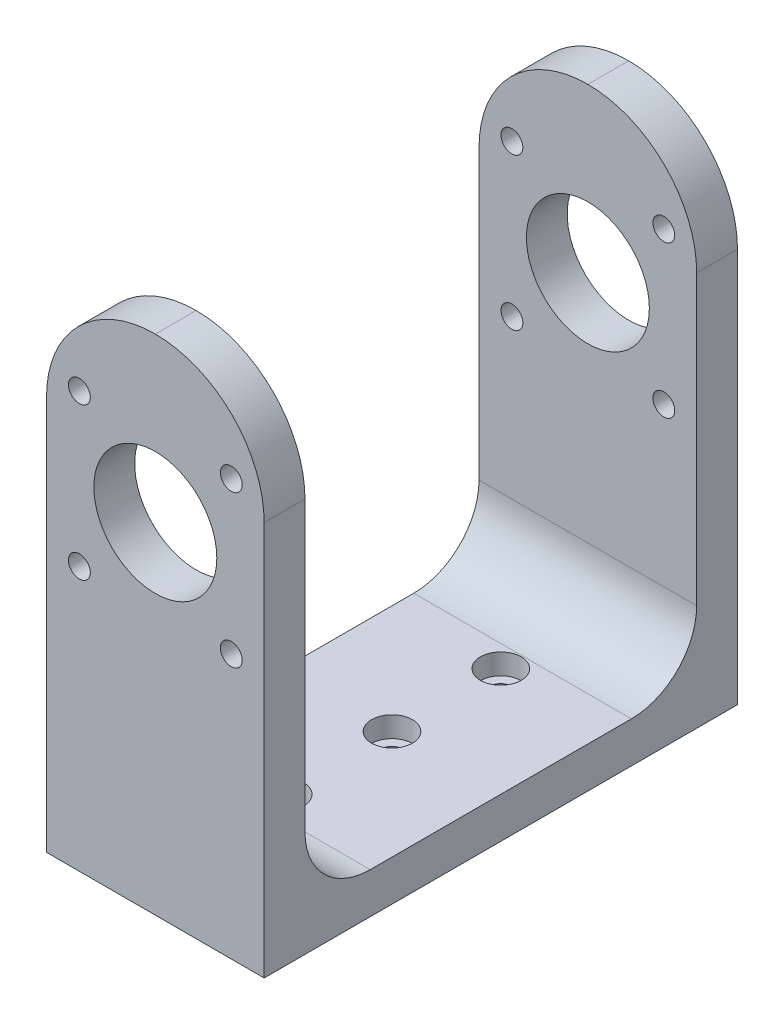
SolidWorks part; units mm, degrees
ref_plane "Front Plane" through (0, 0, 0) normal (0, 0, 1) x (1, 0, 0)
ref_plane "Top Plane" through (0, 0, 0) normal (0, 1, 0) x (1, 0, 0)
ref_plane "Right Plane" through (0, 0, 0) normal (1, 0, 0) x (0, 0, -1)
sketch "Sketch1" plane through (0, 0, 0) normal (0, 1, 0) x (1, 0, 0)
  line L1 (0, 0) -> (50.8, 0)
  line L2 (0, 0) -> (0, 110.49)
  line L3 (0, 110.49) -> (50.8, 110.49)
  line L4 (50.8, 0) -> (50.8, 110.49)
  dimension "D1" = 50.8
  dimension "D2" = 110.49
extrude "Boss-Extrude1" add sketch "Sketch1" along normal blind 9.525 contours L2 L1 L4 L3
sketch "Sketch2" plane through (0, 9.525, 0) normal (0, 1, 0) x (1, 0, 0)
  line L0 (0, 0) -> (0, 110.49) construction
  line L1 (50.8, 110.49) -> (0, 110.49)
  line L2 (50.8, 110.49) -> (50.8, 100.965)
  line L3 (50.8, 100.965) -> (0, 100.965)
  line L4 (0, 110.49) -> (0, 100.965)
  dimension "D1" = 9.525
extrude "Boss-Extrude2" add sketch "Sketch2" along normal blind 107.95 contours L2 L1 L4 L3
sketch "Sketch3" plane through (0, 9.525, 0) normal (0, 1, 0) x (1, 0, 0)
  line L0 (50.8, 0) -> (50.8, 100.965) construction
  line L1 (0, 0) -> (50.8, 0)
  line L2 (0, 0) -> (0, 9.525)
  line L3 (0, 9.525) -> (50.8, 9.525)
  line L4 (50.8, 0) -> (50.8, 9.525)
  dimension "D1" = 9.525
extrude "Boss-Extrude3" add sketch "Sketch3" along normal blind 107.95
sketch "Sketch8" plane through (0, 0, 0) normal (0, 0, 1) x (1, 0, 0)
  line L0 (0, 117.475) -> (50.8, 117.475) construction
  circle A0 centre (25.4, 79.375) radius 14.351
  dimension "D1" = 28.702
  dimension "D2" = 38.1
extrude "Cut-Extrude7" cut sketch "Sketch8" against normal through all contours A0
sketch "Sketch9" plane through (0, 0, -9.525) normal (0, 0, -1) x (-1, 0, 0)
  line L0 (-43.1292, 97.1042) -> (-7.6708, 61.6458) construction
  circle A0 centre (-43.1292, 97.1042) radius 2.5527
  circle A1 centre (-7.6708, 97.1042) radius 2.5527
  circle A2 centre (-7.6708, 61.6458) radius 2.5527
  circle A3 centre (-43.1292, 61.6458) radius 2.5527
  circle A4 centre (-25.4, 79.375) radius 14.351 construction
  dimension "D1" = 35.4584
  dimension "D2" = 35.4584
  dimension "D3" = 35.4584
  dimension "D4" = 5.1054
  dimension "D5" = 17.7292
  dimension "D6" = 17.7292
extrude "Cut-Extrude8" cut sketch "Sketch9" against normal through all
sketch "Sketch10" plane through (0, 0, -110.49) normal (0, 0, -1) x (-1, 0, 0)
  circle A0 centre (-43.1292, 97.1042) radius 2.5527
  circle A1 centre (-7.6708, 97.1042) radius 2.5527
  circle A2 centre (-7.6708, 61.6458) radius 2.5527
  circle A3 centre (-43.1292, 61.6458) radius 2.5527
  circle A4 centre (-7.6708, 61.6458) radius 2.5527 construction
  circle A5 centre (-7.6708, 97.1042) radius 2.5527 construction
  circle A6 centre (-43.1292, 61.6458) radius 2.5527 construction
  circle A7 centre (-43.1292, 97.1042) radius 2.5527 construction
  dimension "D1" = 5.1054
extrude "Cut-Extrude9" cut sketch "Sketch10" against normal through all
fillet "Fillet5" radius 25.4 1 edges at (0, 117.475, -4.7625)
fillet "Fillet6" radius 25.4 1 edges at (50.8, 117.475, -4.7625)
fillet "Fillet7" radius 25.4 1 edges at (0, 117.475, -105.7275)
fillet "Fillet8" radius 25.4 1 edges at (50.8, 117.475, -105.7275)
sketch "Sketch11" plane through (0, 9.525, 0) normal (0, 1, 0) x (1, 0, 0)
  line L1 (50.8, 9.525) -> (50.8, 100.965) construction
  line L2 (50.8, 100.965) -> (0, 100.965) construction
  circle A0 centre (25.4, 55.245) radius 2.5527
  point P9 (50.8, 55.245)
  point P12 (25.4, 100.965)
  dimension "D1" = 5.1054
  dimension "D2" = 0
  dimension "D3" = 0
extrude "Cut-Extrude10" cut sketch "Sketch11" against normal through all
sketch "Sketch12" plane through (0, 9.525, 0) normal (0, 1, 0) x (1, 0, 0)
  circle A0 centre (25.4, 29.845) radius 2.54
  circle A1 centre (25.4, 55.245) radius 2.5527 construction
  circle A2 centre (25.4, 80.645) radius 2.54
  dimension "D1" = 25.4
  dimension "D2" = 25.4
extrude "Cut-Extrude11" cut sketch "Sketch12" against normal through all
fillet "Fillet9" radius 15.24 2 edges at (25.4, 9.525, -9.525) (25.4, 9.525, -100.965)
sketch "Sketch13" plane through (0, 9.525, 0) normal (0, 1, 0) x (1, 0, 0)
  circle A0 centre (25.4, 55.245) radius 4.7625
  circle A1 centre (25.4, 29.845) radius 4.7625
  circle A3 centre (25.4, 80.645) radius 4.7625
  dimension "D1" = 9.525
extrude "Cut-Extrude12" cut sketch "Sketch13" against normal blind 4.826
